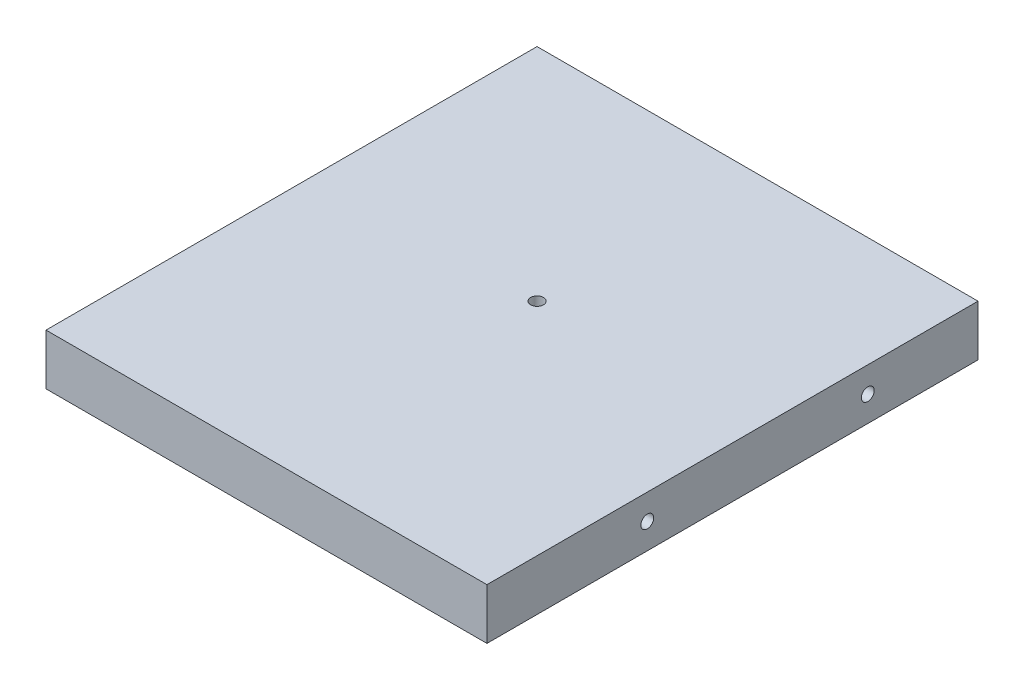
SolidWorks part; units mm, degrees
ref_plane "Front Plane" through (0, 0, 0) normal (0, 0, 1) x (1, 0, 0)
ref_plane "Top Plane" through (0, 0, 0) normal (0, 1, 0) x (1, 0, 0)
ref_plane "Right Plane" through (0, 0, 0) normal (1, 0, 0) x (0, 0, -1)
sketch "Sketch4" plane through (0, 0, 0) normal (0, 1, 0) x (1, 0, 0)
  line L1 (61.7729, 131.481) -> (281.7729, 131.481)
  line L2 (61.7729, 131.481) -> (61.7729, -88.519)
  line L3 (61.7729, -88.519) -> (281.7729, -88.519)
  line L4 (281.7729, 131.481) -> (281.7729, -88.519)
  dimension "D1" = 220
extrude "Boss-Extrude2" add sketch "Sketch4" along normal blind 25.4
sketch "Sketch5" plane through (0, 25.4, 0) normal (0, 1, 0) x (1, 0, 0)
  circle A0 centre (171.7729, 21.481) radius 3.2
extrude "Cut-Extrude1" cut sketch "Sketch5" against normal blind 25.4
sketch "Sketch6" plane through (281.7729, 0, 0) normal (1, 0, 0) x (0, 0, -1)
  circle A0 centre (-33.519, 12.7) radius 3.2
  circle A1 centre (76.481, 12.7) radius 3.2
sketch "Sketch7" plane through (61.7729, 0, 0) normal (-1, 0, 0) x (0, 0, 1)
  circle A0 centre (-76.481, 12.7) radius 3.2
  circle A1 centre (33.519, 12.7) radius 3.2
extrude "Cut-Extrude2" cut sketch "Sketch7" against normal blind 30
extrude "Cut-Extrude4" cut sketch "Sketch6" against normal blind 30
sketch "Sketch13" plane through (0, 0, 88.519) normal (0, 0, 1) x (1, 0, 0)
  line L1 (61.7729, 25.4) -> (281.7729, 25.4)
  line L2 (61.7729, 25.4) -> (61.7729, 0)
  line L3 (61.7729, 0) -> (281.7729, 0)
  line L4 (281.7729, 25.4) -> (281.7729, 0)
  dimension "D1" = 25.4
  dimension "D2" = 220
extrude "Boss-Extrude3" add sketch "Sketch13" along normal blind 25
sketch "Sketch14" plane through (0, 25.4, 0) normal (0, 1, 0) x (1, 0, 0)
  text T0 "<b>Exterior Top</b>" font "Century Gothic" height 10
sketch "Sketch16" plane through (0, 0, 113.519) normal (0, 0, 1) x (1, 0, 0)
  text T0 "Front" font "Century Gothic" height 10
